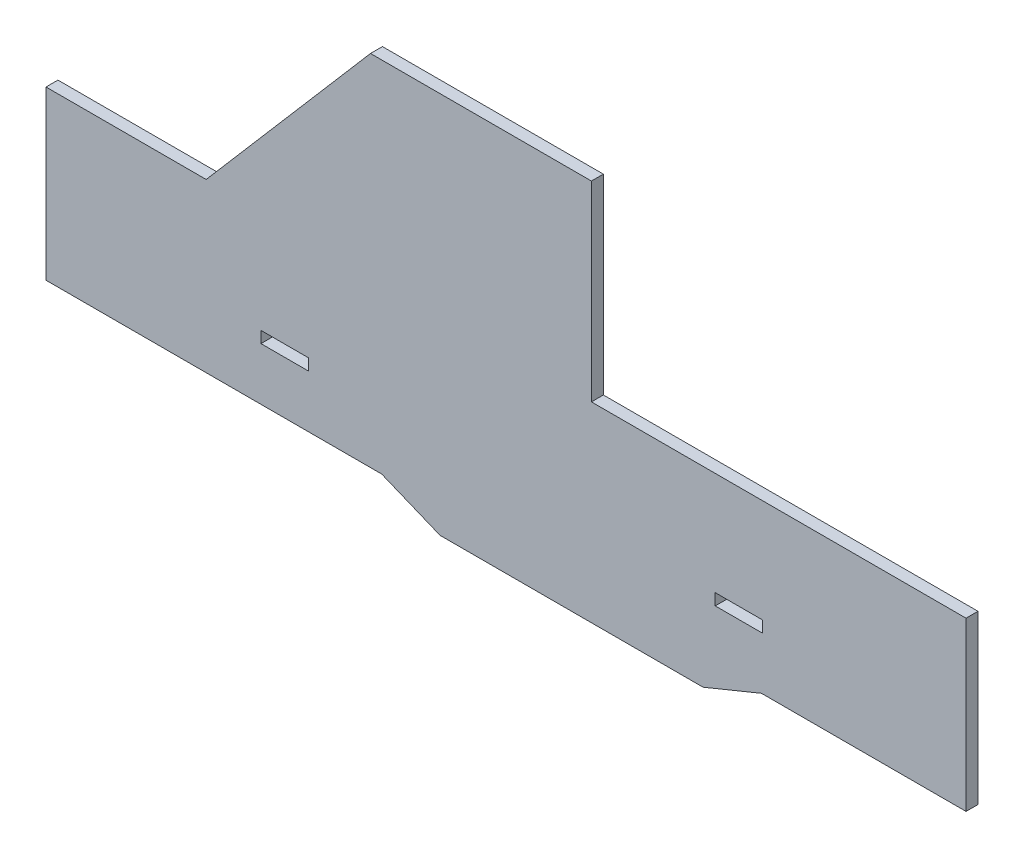
SolidWorks part; units mm, degrees
ref_plane "Front Plane" through (0, 0, 0) normal (0, 0, 1) x (1, 0, 0)
ref_plane "Top Plane" through (0, 0, 0) normal (0, 1, 0) x (1, 0, 0)
ref_plane "Right Plane" through (0, 0, 0) normal (1, 0, 0) x (0, 0, -1)
sketch "Sketch1" plane through (0, 0, 0) normal (0, 0, 1) x (1, 0, 0)
  line L0 (62.1239, 6.35) -> (131.9663, 6.35)
  line L1 (201.8088, 12.7) -> (201.8088, 57.15)
  line L2 (201.8088, 57.15) -> (102.3141, 57.15)
  line L3 (102.3141, 57.15) -> (102.3141, 107.95)
  line L4 (102.3141, 107.95) -> (43.6394, 107.95)
  line L5 (43.6394, 107.95) -> (0, 57.15)
  line L6 (0, 57.15) -> (-42.5392, 57.15)
  line L7 (-42.5392, 57.15) -> (-42.5392, 12.7)
  line L9 (-42.5392, 12.7) -> (46.6174, 12.7)
  line L10 (46.6174, 12.7) -> (62.1239, 6.35)
  line L11 (201.8088, 12.7) -> (147.4729, 12.7)
  line L12 (147.4729, 12.7) -> (131.9663, 6.35)
  dimension "D1" = 244.348
  dimension "D2" = 6.35
  dimension "D3" = 50.8
  dimension "D4" = 44.45
  dimension "D5" = 99.4947
  dimension "D6" = 16.7564
  dimension "D7" = 16.7564
extrude "Main Side" add sketch "Sketch1" along normal blind 3.175
sketch "Sketch2" plane through (0, 0, 3.175) normal (0, 0, 1) x (1, 0, 0)
  line L0 (-39.4912, 57.15) -> (-39.4912, 12.7) construction
  line L15 (0, 57.15) -> (-42.5392, 57.15) construction
  line L16 (-42.5392, 57.15) -> (-42.5392, 12.7) construction
  line L26 (-39.4912, 18.5744) -> (201.8088, 18.5744) construction
  line L27 (201.8088, 12.7) -> (201.8088, 57.15) construction
  line L28 (81.1588, 18.5744) -> (81.1588, 107.95) construction
  line L29 (102.3141, 107.95) -> (43.6394, 107.95) construction
  line L30 (81.1588, 36.7006) -> (201.8088, 36.7006) construction
  line L41 (62.1239, 6.35) -> (131.9663, 6.35) construction
  line L42 (135.1973, 29.718) -> (147.7703, 29.718)
  line L43 (135.1973, 29.718) -> (135.1973, 26.67)
  line L44 (135.1973, 26.67) -> (147.7703, 26.67)
  line L45 (147.7703, 29.718) -> (147.7703, 26.67)
  line L46 (14.5473, 29.718) -> (14.5473, 26.67)
  line L47 (27.1203, 26.67) -> (14.5473, 26.67)
  line L48 (27.1203, 29.718) -> (27.1203, 26.67)
  line L49 (27.1203, 29.718) -> (14.5473, 29.718)
  line L51 (-42.5392, 12.7) -> (46.6174, 12.7) construction
  point P2 (-39.4912, 12.7)
  point P20 (141.4838, 29.718)
  point P21 (141.4838, 36.7006)
  point P30 (0, 0)
  dimension "D1" = 12.573
  dimension "D2" = 3.048
  dimension "D3" = 20.32
  dimension "D4" = 3.048
extrude "Bottom Plate Holes" cut sketch "Sketch2" against normal through all
